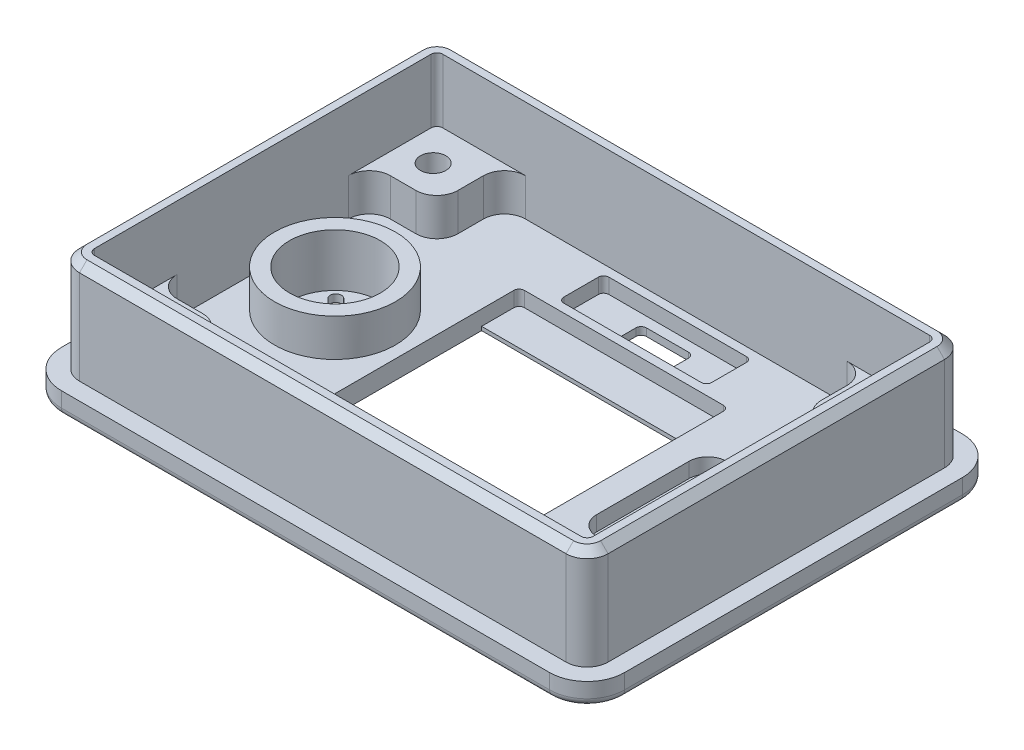
SolidWorks part; units mm, degrees
ref_plane "Front Plane" through (0, 0, 0) normal (0, 0, 1) x (1, 0, 0)
ref_plane "Top Plane" through (0, 0, 0) normal (0, 1, 0) x (1, 0, 0)
ref_plane "Right Plane" through (0, 0, 0) normal (1, 0, 0) x (0, 0, -1)
sketch "Sketch1" plane through (0, 0, 0) normal (0, 1, 0) x (1, 0, 0)
  line L1 (-37.5, -27.5) -> (37.5, -27.5)
  line L2 (-37.5, -27.5) -> (-37.5, 27.5)
  line L3 (-37.5, 27.5) -> (37.5, 27.5)
  line L4 (37.5, -27.5) -> (37.5, 27.5)
  line L5 (-37.5, -27.5) -> (37.5, 27.5) construction
  line L6 (-37.5, 27.5) -> (37.5, -27.5) construction
  point P0 (0, 0)
  dimension "D1" = 75
  dimension "D2" = 55
extrude "Boss-Extrude1" add sketch "Sketch1" along normal blind 3
sketch "Sketch2" plane through (0, 3, 0) normal (0, 1, 0) x (1, 0, 0)
  line L0 (6.75, -9.9) -> (13.95, -9.9)
  line L1 (-13.95, -9.9) -> (-6.75, -9.9)
  line L2 (-13.95, -9.9) -> (-13.95, 9.9)
  line L3 (-13.95, 9.9) -> (13.95, 9.9)
  line L4 (13.95, -9.9) -> (13.95, 9.9)
  line L5 (-13.95, -9.9) -> (13.95, 9.9) construction
  line L6 (-13.95, 9.9) -> (13.95, -9.9) construction
  line L8 (-6.75, -9.9) -> (-6.75, -12.3)
  line L9 (-6.75, -12.3) -> (6.75, -12.3)
  line L10 (6.75, -9.9) -> (6.75, -12.3)
  line L16 (-13.95, -14.9) -> (13.95, -14.9)
  line L17 (-13.95, -14.9) -> (-13.95, 14.9)
  line L18 (-13.95, 14.9) -> (13.95, 14.9)
  line L19 (13.95, -14.9) -> (13.95, 14.9)
  line L20 (-13.95, -14.9) -> (13.95, 14.9) construction
  line L21 (-13.95, 14.9) -> (13.95, -14.9) construction
  point P0 (0, 0)
  point P10 (0, -12.3)
  point P11 (0, 0)
  point P12 (0, 0)
  dimension "D2" = 22.2
  dimension "D1" = 27.9
  dimension "D3" = 19.8
  dimension "D4" = 13.5
  dimension "D5" = 5
sketch "Sketch11" plane through (0, 3, 0) normal (0, 1, 0) x (1, 0, 0)
  line L0 (33.2, 23.2) -> (-33.2, 23.2)
  line L1 (-33.2, 23.2) -> (-33.2, -23.2)
  line L2 (-33.2, -23.2) -> (33.2, -23.2)
  line L3 (33.2, -23.2) -> (33.2, 23.2)
  line L4 (-33.2, 14.2) -> (-24.2, 14.2)
  line L5 (-24.2, 14.2) -> (-24.2, 23.2)
  line L6 (0, 23.2) -> (0, -23.2) construction
  line L7 (-33.2, 0) -> (33.2, 0) construction
  line L8 (-33.2, 14.2) -> (-33.2, 23.2)
  line L9 (-24.2, 23.2) -> (-33.2, 23.2)
  line L14 (-35.2, 25.2) -> (-35.2, -25.2)
  line L15 (-35.2, -25.2) -> (35.2, -25.2)
  line L16 (35.2, -25.2) -> (35.2, 25.2)
  line L17 (35.2, 25.2) -> (-35.2, 25.2)
  line L18 (-35.2, 25.2) -> (-35.2, -25.2)
  line L19 (-35.2, -25.2) -> (35.2, -25.2)
  line L20 (35.2, -25.2) -> (35.2, 25.2)
  line L21 (35.2, 25.2) -> (-35.2, 25.2)
  line L22 (24.2, 23.2) -> (33.2, 23.2)
  line L23 (24.2, 14.2) -> (24.2, 23.2)
  line L24 (33.2, 14.2) -> (24.2, 14.2)
  line L25 (33.2, 14.2) -> (33.2, 23.2)
  line L26 (24.2, -23.2) -> (33.2, -23.2)
  line L27 (24.2, -14.2) -> (24.2, -23.2)
  line L28 (33.2, -14.2) -> (24.2, -14.2)
  line L29 (33.2, -14.2) -> (33.2, -23.2)
  line L30 (-24.2, -23.2) -> (-33.2, -23.2)
  line L31 (-24.2, -14.2) -> (-24.2, -23.2)
  line L32 (-33.2, -14.2) -> (-24.2, -14.2)
  line L33 (-33.2, -14.2) -> (-33.2, -23.2)
  dimension "D3" = 9
  dimension "D1" = 2.3
  dimension "D2" = 2
extrude "Boss-Extrude2" add sketch "Sketch11" along normal blind 13.5 contours L20 L21 L18 L19 region at (0, 3, -24.3342)
extrude "Boss-Extrude4" add sketch "Sketch11<3>" along normal blind 5 contours L27 | L33 L32 L31 L30 | L8 L4 L5 L9 | L25 L24 L23 L22 region at (28.7, 3, 18.7)
sketch "Sketch11<3>" plane through (0, 3, 0) normal (0, 1, 0) x (1, 0, 0) same geometry as "Sketch11"
extrude "Cut-Extrude1" cut sketch "Sketch2" against normal through all contours L10 L0 L4 L3 L2 L1 L8 L9 region at (0, 3, 0.615)
extrude "Cut-Extrude2" cut sketch "Sketch2<4>" against normal offset from surface (2 mm away) 1 contours L3 L19 L18 L17 | L16 L19 L0 L10 L9 L8 L1 L17 region at (0, 3, 12.7933) region at (0, 3, -12.4) up to face at (0, 0, 0)
sketch "Sketch2<4>" plane through (0, 3, 0) normal (0, 1, 0) x (1, 0, 0) same geometry as "Sketch2"
fillet "Fillet1" radius 5 4 edges at (-37.5, 1.5, 27.5) (37.5, 1.5, 27.5) (37.5, 1.5, -27.5) (-37.5, 1.5, -27.5)
fillet "Fillet2" radius 2.8 16 edges at (-35.2, 9.75, -25.2) (-35.2, 9.75, 25.2) (35.2, 9.75, 25.2) (35.2, 9.75, -25.2) (24.2, 5.5, 23.2) (24.2, 5.5, 14.2) (33.2, 5.5, 14.2) (33.2, 5.5, -14.2) (24.2, 5.5, -23.2) (24.2, 5.5, -14.2) (-24.2, 5.5, -23.2) (-24.2, 5.5, -14.2) (-33.2, 5.5, -14.2) (-24.2, 5.5, 23.2) (-24.2, 5.5, 14.2) (-33.2, 5.5, 14.2)
fillet "Fillet3" radius 1 8 edges at (36.0355, 0, -26.0355) (37.5, 0, 0) (36.0355, 0, 26.0355) (0, 0, 27.5) (-36.0355, 0, 26.0355) (-37.5, 0, 0) (-36.0355, 0, -26.0355) (0, 0, -27.5)
sketch "Sketch13" plane through (0, 3, 0) normal (0, 1, 0) x (1, 0, 0)
  line L0 (-13.95, 0) -> (-33.2, 0) construction
  line L1 (-13.95, -14.9) -> (-13.95, 14.9) construction
  line L3 (-33.2, 11.4) -> (-33.2, -11.4) construction
  circle A0 centre (-23.575, 0) radius 6.05
  circle A2 centre (-23.575, 0) radius 8.05
  point P6 (-23.575, 0)
  dimension "D1" = 12.1
  dimension "D2" = 2
extrude "Boss-Extrude3" add sketch "Sketch13" along normal blind 5
sketch "Sketch15" plane through (0, 3, 0) normal (0, 1, 0) x (1, 0, 0)
  circle A0 centre (-23.575, 0) radius 6.05 construction
  circle A1 centre (-23.575, 0) radius 6.05
extrude "Cut-Extrude4" cut sketch "Sketch15" against normal offset from surface (2 mm away) 1 up to face at (0, 0, 0)
sketch "Sketch14" plane through (0, 3, 0) normal (0, 1, 0) x (1, 0, 0)
  line L0 (-26.325, 0) -> (-28.325, 0) construction
  line L1 (-26.325, -0.75) -> (-28.325, -0.75)
  line L2 (-26.325, 0.75) -> (-28.325, 0.75)
  line L3 (-25.4629, 2) -> (-26.8771, 3.4142) construction
  line L4 (-25.9932, 1.4697) -> (-27.4074, 2.8839)
  line L5 (-24.9326, 2.5303) -> (-26.3468, 3.9445)
  line L6 (-25.4629, -2) -> (-26.8771, -3.4142) construction
  line L7 (-24.9326, -2.5303) -> (-26.3468, -3.9445)
  line L8 (-25.9932, -1.4697) -> (-27.4074, -2.8839)
  line L9 (-23.575, 1.35) -> (-23.575, -1.35) construction
  line L10 (-21.6871, 2) -> (-20.2729, 3.4142) construction
  line L11 (-21.1568, 1.4697) -> (-19.7426, 2.8839)
  line L12 (-22.2174, 2.5303) -> (-20.8032, 3.9445)
  line L13 (-20.825, 0) -> (-18.825, 0) construction
  line L14 (-20.825, -0.75) -> (-18.825, -0.75)
  line L15 (-20.825, 0.75) -> (-18.825, 0.75)
  line L16 (-21.6871, -2) -> (-20.2729, -3.4142) construction
  line L17 (-22.2174, -2.5303) -> (-20.8032, -3.9445)
  line L18 (-21.1568, -1.4697) -> (-19.7426, -2.8839)
  circle A0 centre (-23.575, 0) radius 1.35
  arc A1 (-26.325, -0.75) -> (-26.325, 0.75) centre (-26.325, 0) ccw
  arc A2 (-28.325, 0.75) -> (-28.325, -0.75) centre (-28.325, 0) ccw
  arc A3 (-25.9932, 1.4697) -> (-24.9326, 2.5303) centre (-25.4629, 2) ccw
  arc A4 (-26.3468, 3.9445) -> (-27.4074, 2.8839) centre (-26.8771, 3.4142) ccw
  arc A5 (-24.9326, -2.5303) -> (-25.9932, -1.4697) centre (-25.4629, -2) ccw
  arc A6 (-27.4074, -2.8839) -> (-26.3468, -3.9445) centre (-26.8771, -3.4142) ccw
  circle A7 centre (-23.575, 0) radius 3.75 construction
  arc A8 (-21.1568, 1.4697) -> (-22.2174, 2.5303) centre (-21.6871, 2) cw
  arc A9 (-25.4629, -2) -> (-25.4629, 2) centre (-23.574, 0) cw construction
  arc A10 (-20.8032, 3.9445) -> (-19.7426, 2.8839) centre (-20.2729, 3.4142) cw
  arc A11 (-20.825, -0.75) -> (-20.825, 0.75) centre (-20.825, 0) cw
  arc A12 (-18.825, 0.75) -> (-18.825, -0.75) centre (-18.825, 0) cw
  arc A13 (-22.2174, -2.5303) -> (-21.1568, -1.4697) centre (-21.6871, -2) cw
  arc A14 (-19.7426, -2.8839) -> (-20.8032, -3.9445) centre (-20.2729, -3.4142) cw
  circle A15 centre (-23.575, 0) radius 6.05 construction
  point P4 (-27.325, 0)
  point P9 (-26.17, 2.7071)
  point P16 (-26.17, -2.7071)
  point P24 (-26.325, 0)
  point P32 (-20.98, 2.7071)
  point P39 (-19.825, 0)
  point P46 (-20.98, -2.7071)
  dimension "D1" = 2.7
  dimension "D2" = 7.5
  dimension "D3" = 45
  dimension "D4" = 1.5
  dimension "D5" = 1.5
  dimension "D6" = 1.5
  dimension "D7" = 2
  dimension "D8" = 4
extrude "Cut-Extrude3" cut sketch "Sketch14" against normal through all
sketch "Sketch16" plane through (0, 3, 0) normal (0, 1, 0) x (1, 0, 0)
  line L0 (13.95, 0) -> (33.2, 0) construction
  line L1 (19.925, -7.65) -> (27.225, -7.65)
  line L2 (18.425, -6.15) -> (18.425, 6.15)
  line L3 (19.925, 7.65) -> (27.225, 7.65)
  line L4 (28.725, -6.15) -> (28.725, 6.15)
  line L5 (18.425, -7.65) -> (28.725, 7.65) construction
  line L6 (18.425, 7.65) -> (28.725, -7.65) construction
  line L7 (13.95, -14.9) -> (13.95, 14.9) construction
  line L21 (19.925, 8.65) -> (27.225, 8.65)
  line L22 (29.725, -6.15) -> (29.725, 6.15)
  line L23 (19.925, -8.65) -> (27.225, -8.65)
  line L24 (17.425, -6.15) -> (17.425, 6.15)
  line L25 (33.2, -11.4) -> (33.2, 11.4) construction
  arc A0 (27.225, -7.65) -> (28.725, -6.15) centre (27.225, -6.15) ccw
  arc A1 (18.425, 6.15) -> (19.925, 7.65) centre (19.925, 6.15) cw
  arc A2 (19.925, -7.65) -> (18.425, -6.15) centre (19.925, -6.15) cw
  arc A3 (27.225, 7.65) -> (28.725, 6.15) centre (27.225, 6.15) cw
  arc A16 (27.225, 8.65) -> (29.725, 6.15) centre (27.225, 6.15) cw
  arc A17 (27.225, -8.65) -> (29.725, -6.15) centre (27.225, -6.15) ccw
  arc A18 (19.925, -8.65) -> (17.425, -6.15) centre (19.925, -6.15) cw
  arc A19 (17.425, 6.15) -> (19.925, 8.65) centre (19.925, 6.15) cw
  point P0 (23.575, 0)
  point P12 (23.575, 0)
  dimension "D3" = 1.5
  dimension "D1" = 10.3
  dimension "D2" = 15.3
  dimension "D4" = 1
extrude "Cut-Extrude5" cut sketch "Sketch16" against normal through all contours L2 A1 L3 A3 L4 A0 L1 A2
extrude "Cut-Extrude6" cut sketch "Sketch16<3>" against normal offset from surface (2 mm away) 1 up to face at (-20.98, 0, -2.7071)
sketch "Sketch16<3>" plane through (0, 3, 0) normal (0, 1, 0) x (1, 0, 0) same geometry as "Sketch16"
sketch "Sketch17" plane through (0, 3, 0) normal (0, 1, 0) x (1, 0, 0)
  line L0 (0, 14.9) -> (0, 23.2) construction
  line L1 (-9.85, 22.05) -> (9.85, 22.05)
  line L2 (-9.85, 22.05) -> (-9.85, 16.05)
  line L3 (-9.85, 16.05) -> (9.85, 16.05)
  line L4 (9.85, 22.05) -> (9.85, 16.05)
  line L5 (-9.85, 22.05) -> (9.85, 16.05) construction
  line L6 (-9.85, 16.05) -> (9.85, 22.05) construction
  line L7 (-13.95, 14.9) -> (13.95, 14.9) construction
  line L9 (21.4, 23.2) -> (-21.4, 23.2) construction
  point P0 (0, 19.05)
  point P12 (0, 19.05)
  dimension "D1" = 6
  dimension "D2" = 19.7
extrude "Cut-Extrude7" cut sketch "Sketch17" against normal offset from surface (2 mm away) 1 up to face at (-20.98, 0, -2.7071)
sketch "Sketch18" plane through (0, 1, 0) normal (0, 1, 0) x (1, 0, 0)
  line L0 (0, 16.05) -> (0, 22.05) construction
  line L1 (-9.85, 16.05) -> (9.85, 16.05) construction
  line L2 (9.85, 22.05) -> (-9.85, 22.05) construction
  line L4 (-3.5, 17.4) -> (3.5, 17.4)
  line L5 (-3.5, 17.4) -> (-3.5, 20.7)
  line L6 (-3.5, 20.7) -> (3.5, 20.7)
  line L7 (3.5, 17.4) -> (3.5, 20.7)
  line L8 (-3.5, 17.4) -> (3.5, 20.7) construction
  line L9 (-3.5, 20.7) -> (3.5, 17.4) construction
  point P6 (0, 19.05)
  dimension "D1" = 3.3
  dimension "D2" = 7
extrude "Cut-Extrude8" cut sketch "Sketch18" against normal through all
chamfer "Chamfer1" distance 0.5 angle 45 16 edges at (6.75, 0, 11.1) (0, 0, 12.3) (-6.75, 0, 11.1) (10.35, 0, 9.9) (-10.35, 0, 9.9) (-13.95, 0, 0) (0, 0, -9.9) (13.95, 0, 0) (18.8643, 0, -7.2107) (18.425, 0, 0) (23.575, 0, -7.65) (18.8643, 0, 7.2107) (28.2857, 0, -7.2107) (23.575, 0, 7.65) (28.725, 0, 0) (28.2857, 0, 7.2107)
fillet "Fillet4" radius 0.7 12 edges at (9.85, 2, -16.05) (9.85, 2, -22.05) (-9.85, 2, -22.05) (-9.85, 2, -16.05) (-3.5, 0.5, -17.4) (3.5, 0.5, -17.4) (-3.5, 0.5, -20.7) (3.5, 0.5, -20.7) (-13.95, 2, 14.9) (13.95, 2, 14.9) (13.95, 2, -14.9) (-13.95, 2, -14.9)
fillet "Fillet5" radius 0.8 4 edges at (-33.2, 12.25, 23.2) (33.2, 12.25, 23.2) (33.2, 12.25, -23.2) (-33.2, 12.25, -23.2)
chamfer "Chamfer2" distance 1 angle 45 8 edges at (35.2, 16.5, 0) (34.3799, 16.5, -24.3799) (34.3799, 16.5, 24.3799) (0, 16.5, -25.2) (0, 16.5, 25.2) (-34.3799, 16.5, -24.3799) (-34.3799, 16.5, 24.3799) (-35.2, 16.5, 0)
sketch "Sketch19" plane through (0, 0, 0) normal (0, -1, 0) x (1, 0, 0)
  line L1 (-29, -18.5) -> (29, -18.5) construction
  line L2 (-29, -18.5) -> (-29, 18.5) construction
  line L3 (-29, 18.5) -> (29, 18.5) construction
  line L4 (29, -18.5) -> (29, 18.5) construction
  line L5 (-29, -18.5) -> (29, 18.5) construction
  line L6 (-29, 18.5) -> (29, -18.5) construction
  point P0 (0, 0)
  point P7 (-29, 18.5)
  point P8 (29, 18.5)
  point P9 (29, -18.5)
  point P10 (-29, -18.5)
  dimension "D1" = 58
  dimension "D2" = 37
hole_wizard "CBORE for M3 Hex Socket Head Cap Screw1" positions "Sketch19" profile "Sketch20" counterbore size "M3" standard "ISO" end condition through all
sketch "Sketch20" plane through (-29, 0, -18.5) normal (1, 0, 0) x (0, 0, -1)
  line L0 (0, 0) -> (0, 16.5)
  line L1 (0, 16.5) -> (1.7, 16.5)
  line L3 (1.7, 16.5) -> (1.7, 3.1)
  line L4 (1.7, 3.1) -> (2.85, 3.1)
  line L5 (2.85, 3.1) -> (2.85, 0)
  line L7 (2.85, 0) -> (0, 0)
  line L11 (0, -6.35) -> (0, 107.95) construction
  dimension "Thru Hole Dia." = 3.4
  dimension "Thru Hole Depth" = 16.5
  dimension "C'Bore Dia." = 5.7
  dimension "C'Bore Depth" = 3.1
